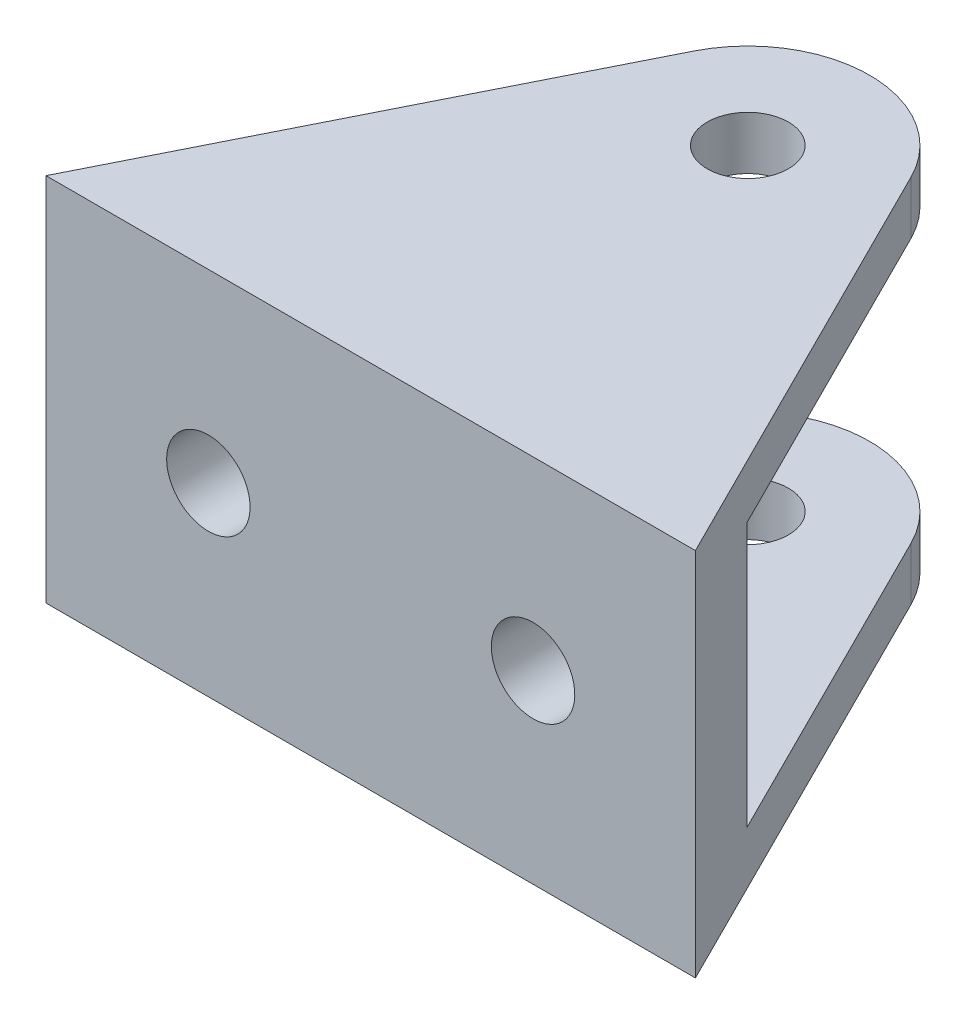
SolidWorks part; units mm, degrees
material "6061-T6 (SS)"
ref_plane "X-Y Datum" through (0, 0, 0) normal (0, 0, 1) x (1, 0, 0)
ref_plane "X-Z Datum" through (0, 0, 0) normal (0, 1, 0) x (1, 0, 0)
ref_plane "Y-Z Datum" through (0, 0, 0) normal (1, 0, 0) x (0, 0, -1)
sketch "Sketch1" plane through (0, 0, 0) normal (1, 0, 0) x (0, 0, -1)
  line L0 (0, 0) -> (0, 28.956)
  line L1 (0, 28.956) -> (39.8563, 28.956)
  line L2 (39.8563, 28.956) -> (39.8563, 24.8031)
  line L3 (39.8563, 24.8031) -> (8.1063, 24.8031)
  line L4 (8.1063, 24.8031) -> (8.1063, 4.1529)
  line L5 (8.1063, 4.1529) -> (39.8563, 4.1529)
  line L6 (39.8563, 4.1529) -> (39.8563, 0)
  line L7 (39.8563, 0) -> (0, 0)
  line L8 (27.1563, 28.956) -> (27.1563, 0) construction
  dimension "D1" = 20.6502
  dimension "D2" = 12.7
  dimension "D3" = 31.75
  dimension "D4" = 28.956
extrude "Boss-Extrude1" add sketch "Sketch1" along normal blind 50.8
sketch "Sketch2" plane through (0, 0, -8.1063) normal (0, 0, -1) x (-1, 0, 0)
  line L0 (-25.4, 24.8031) -> (-25.4, 4.1529) construction
  line L1 (-50.8, 24.8031) -> (0, 24.8031) construction
  line L2 (-50.8, 4.1529) -> (0, 4.1529) construction
  line L3 (-38.1, 14.478) -> (-12.7, 14.478) construction
  point P8 (-25.4, 14.478)
  point P9 (-25.4, 14.478)
  point P11 (-38.1, 14.478)
  point P12 (-12.7, 14.478)
  dimension "D1" = 25.4
hole_wizard "CBORE for 1/4 Binding Head Machine Screw1" positions "Sketch2" profile "Sketch3" counterbore size "1/4" standard "ANSI Inch" end condition through all
sketch "Sketch3" plane through (12.7, 14.478, -8.1063) normal (1, 0, 0) x (0, 1, 0)
  line L0 (0, 0) -> (0, 8.1063)
  line L1 (0, 8.1063) -> (3.2639, 8.1063)
  line L3 (3.2639, 8.1063) -> (3.2639, 3.302)
  line L4 (3.2639, 3.302) -> (7.1437, 3.302)
  line L5 (7.1437, 3.302) -> (7.1437, 0)
  line L7 (7.1437, 0) -> (0, 0)
  line L11 (0, -6.35) -> (0, 107.95) construction
  dimension "Thru Hole Dia." = 6.5278
  dimension "Thru Hole Depth" = 8.1063
  dimension "C'Bore Dia." = 14.2875
  dimension "C'Bore Depth" = 3.302
sketch "Sketch4" plane through (0, 0, 0) normal (0, -1, 0) x (1, 0, 0)
  line L0 (25.4, -39.8563) -> (25.4, 0) construction
  line L1 (50.8, -39.8563) -> (0, -39.8563) construction
  line L2 (50.8, 0) -> (0, 0) construction
  line L3 (0, 0) -> (16.8808, -33.7579)
  line L4 (50.8, 0) -> (33.9192, -33.7579)
  line L5 (0, 0) -> (0, -39.8563)
  line L6 (0, -39.8563) -> (50.8, -39.8563)
  line L7 (50.8, -39.8563) -> (50.8, 0)
  circle A0 centre (25.4, -29.4978) radius 3.175
  arc A1 (16.8808, -33.7579) -> (33.9192, -33.7579) centre (25.4, -29.4978) ccw
  dimension "D1" = 6.35
  dimension "D2" = 6.35
extrude "Cut-Extrude1" cut sketch "Sketch4" against normal up to surface (28.956 mm away) up to face at (25.4, 28.956, -19.9282)
